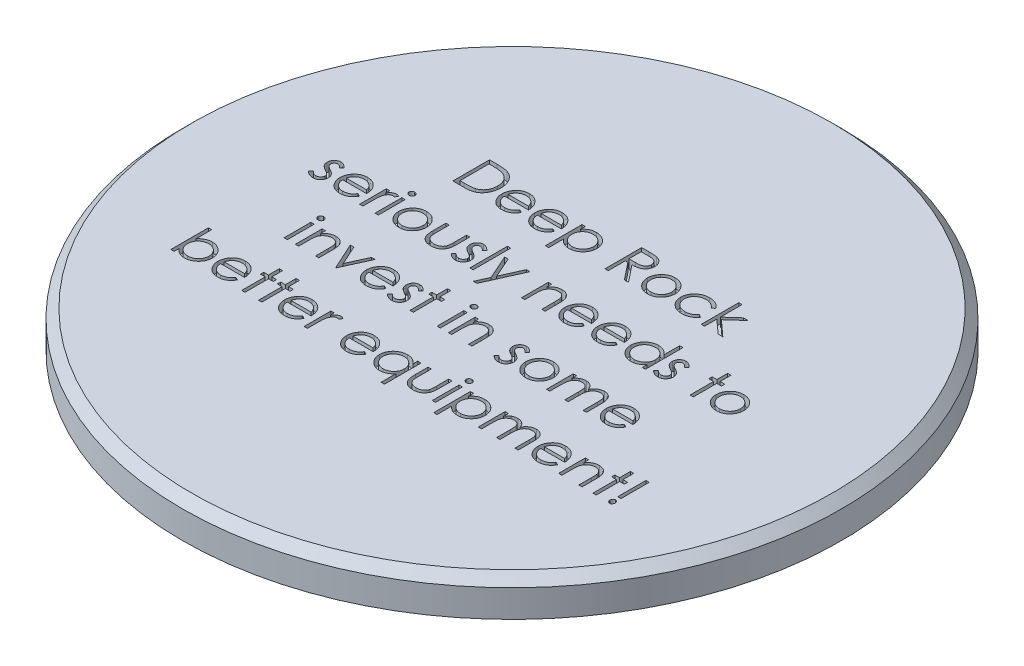
SolidWorks part; units mm, degrees
ref_plane "Front Plane" through (0, 0, 0) normal (0, 0, 1) x (1, 0, 0)
ref_plane "Top Plane" through (0, 0, 0) normal (0, 1, 0) x (1, 0, 0)
ref_plane "Right Plane" through (0, 0, 0) normal (1, 0, 0) x (0, 0, -1)
sketch "Sketch1" plane through (0, 0, 0) normal (0, 1, 0) x (1, 0, 0)
  circle A0 centre (0, 0) radius 57.15
  dimension "D1" = 114.3
extrude "Boss-Extrude1" add sketch "Sketch1" along normal blind 6.35 contours A0 | A0 region at (0, 0, 0)
sketch "Sketch2" plane through (0, 6.35, 0) normal (0, 1, 0) x (1, 0, 0)
  line L0 (-55.4163, 13.97) -> (55.4163, 13.97) construction
  circle A0 centre (0, 0) radius 57.15 construction
  circle A1 centre (0, 0) radius 57.15 construction
  text T0 "Deep Rock \r\nseriously needs to \r\ninvest in some \r\nbetter equipment!" font "Century Gothic" height in points 24
  dimension "D1" = 13.97
extrude "Cut-Extrude1" cut sketch "Sketch2" against normal blind 1.5875
chamfer "Chamfer1" distance 1.5875 angle 45 1 edges at (0, 6.35, 57.15)
